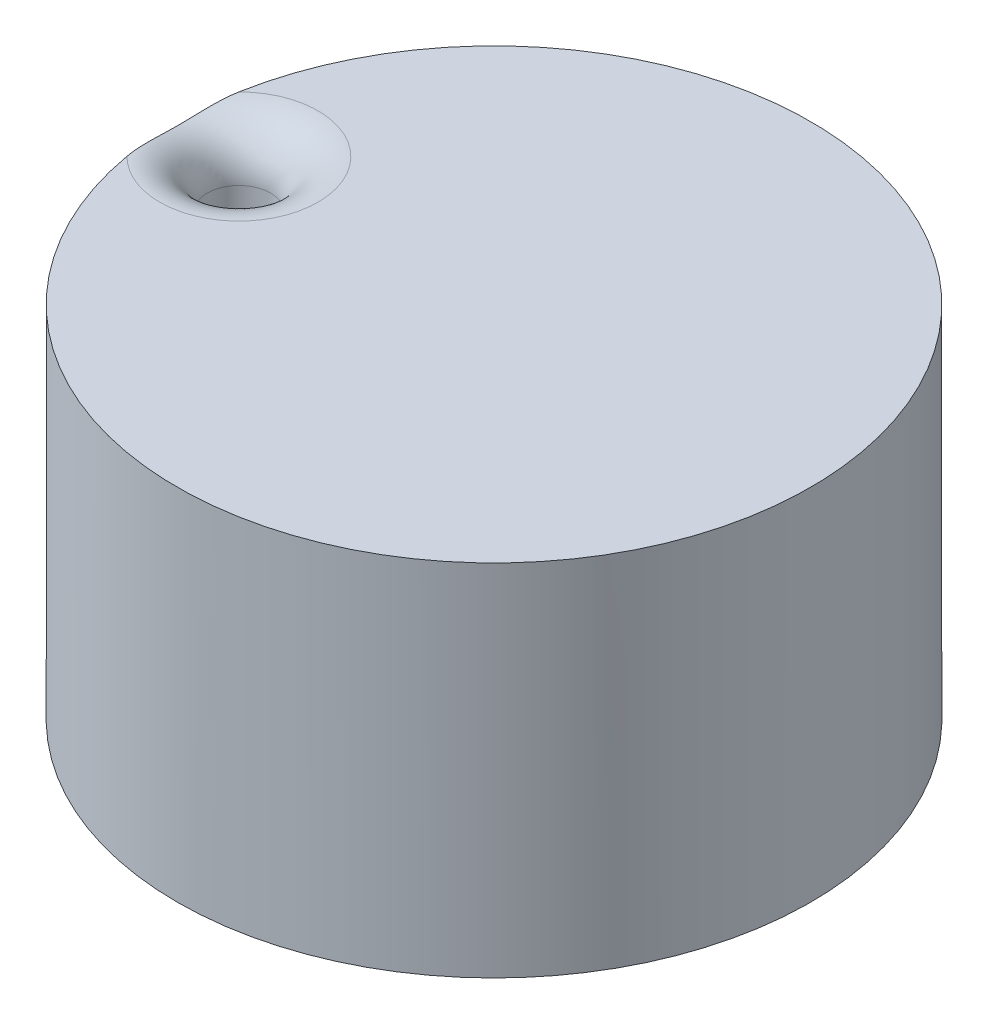
SolidWorks part; units mm, degrees
ref_plane "Front Plane" through (0, 0, 0) normal (0, 0, 1) x (1, 0, 0)
ref_plane "Top Plane" through (0, 0, 0) normal (0, 1, 0) x (1, 0, 0)
ref_plane "Right Plane" through (0, 0, 0) normal (1, 0, 0) x (0, 0, -1)
sketch "Sketch2" plane through (0, 0, 0) normal (0, 1, 0) x (1, 0, 0)
  circle A0 centre (0, 0) radius 50.8
extrude "Boss-Extrude1" add sketch "Sketch2" along normal blind 57.658
sketch "Sketch3" plane through (0, 57.658, 0) normal (0, 1, 0) x (1, 0, 0)
  circle A1 centre (-41.0118, 0.0886) radius 5.08
extrude "Cut-Extrude1" cut sketch "Sketch3" against normal blind 57.658 contours A1
fillet "Fillet1" radius 7.62 1 edges at (-41.0118, 57.658, 4.9914)
sketch "Sketch4" plane through (0, 57.658, 0) normal (0, 1, 0) x (1, 0, 0)
  circle A1 centre (-26.162, 0) radius 3.175
  circle A2 centre (26.162, 0) radius 3.175
  circle A3 centre (0, 26.162) radius 3.175
  circle A4 centre (0, -26.162) radius 3.175
